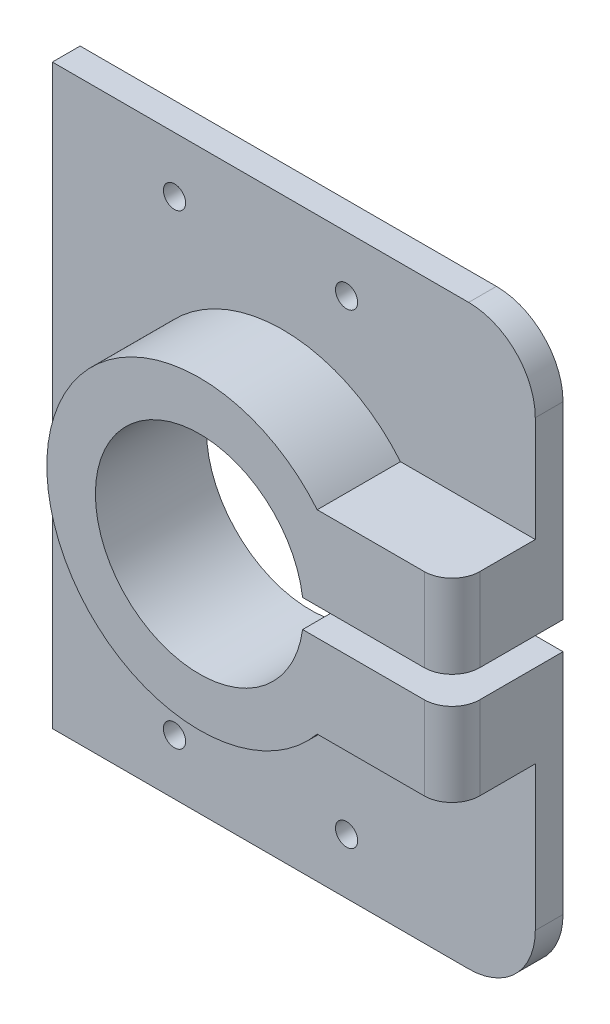
SolidWorks part; units mm, degrees
ref_plane "Front Plane" through (0, 0, 0) normal (0, 0, 1) x (1, 0, 0)
ref_plane "Top Plane" through (0, 0, 0) normal (0, 1, 0) x (1, 0, 0)
ref_plane "Right Plane" through (0, 0, 0) normal (1, 0, 0) x (0, 0, -1)
sketch "Sketch1" plane through (0, 0, 0) normal (0, 0, 1) x (1, 0, 0)
  line L0 (31.5, 52) -> (-43.5, 52)
  line L1 (-43.5, 52) -> (-43.5, -52)
  line L2 (-43.5, -52) -> (31.5, -52)
  line L3 (43.5, -40) -> (43.5, -14)
  line L4 (43.5, -14) -> (19.2132, -14)
  line L5 (19.2132, 21) -> (43.5, 21)
  line L6 (43.5, 21) -> (43.5, 40)
  line L7 (43.5, 21) -> (39.5, 21)
  line L8 (39.5, 6) -> (43.5, 6)
  line L9 (43.5, 6) -> (43.5, 21)
  line L10 (39.5, -14) -> (43.5, -14)
  line L11 (43.5, -14) -> (43.5, 1)
  line L12 (43.5, 1) -> (39.5, 1)
  line L13 (39.5, 21) -> (19.2132, 21)
  line L14 (19.2132, -14) -> (39.5, -14)
  line L15 (39.5, 1) -> (16.5826, 1)
  line L16 (16.5826, 6) -> (39.5, 6)
  circle A0 centre (-21.5, 42) radius 2
  arc A1 (43.5, 40) -> (31.5, 52) centre (31.5, 40) ccw
  arc A2 (31.5, -52) -> (43.5, -40) centre (31.5, -40) ccw
  arc A3 (19.2132, 21) -> (19.2132, -14) centre (-2, 3.5) ccw
  circle A4 centre (9.5, -42) radius 2
  circle A5 centre (-21.5, -42) radius 2
  circle A6 centre (9.5, 42) radius 2
  arc A7 (19.2132, 21) -> (19.2132, -14) centre (-2, 3.5) ccw
  arc A8 (16.5826, 6) -> (16.5826, 1) centre (-2, 3.5) ccw
extrude "Boss-Extrude1" add sketch "Sketch1" along normal blind 5 contours A3 L5 L6 A1 L0 L1 L2 A2 L3 L4 A6 A5 A4 A0 region at (39.0265, 47.5265, 0)
extrude "Boss-Extrude2" add sketch "Sketch1<3>" along normal blind 20 contours A8 L16 L8 L9 L5 A3 L4 L11 L12 L15 region at (42.586, 13.5, 0)
sketch "Sketch1<3>" plane through (0, 0, 0) normal (0, 0, 1) x (1, 0, 0) same geometry as "Sketch1"
fillet "Fillet1" radius 5 2 edges at (43.5, -6.5, 20) (43.5, 13.5, 20)
